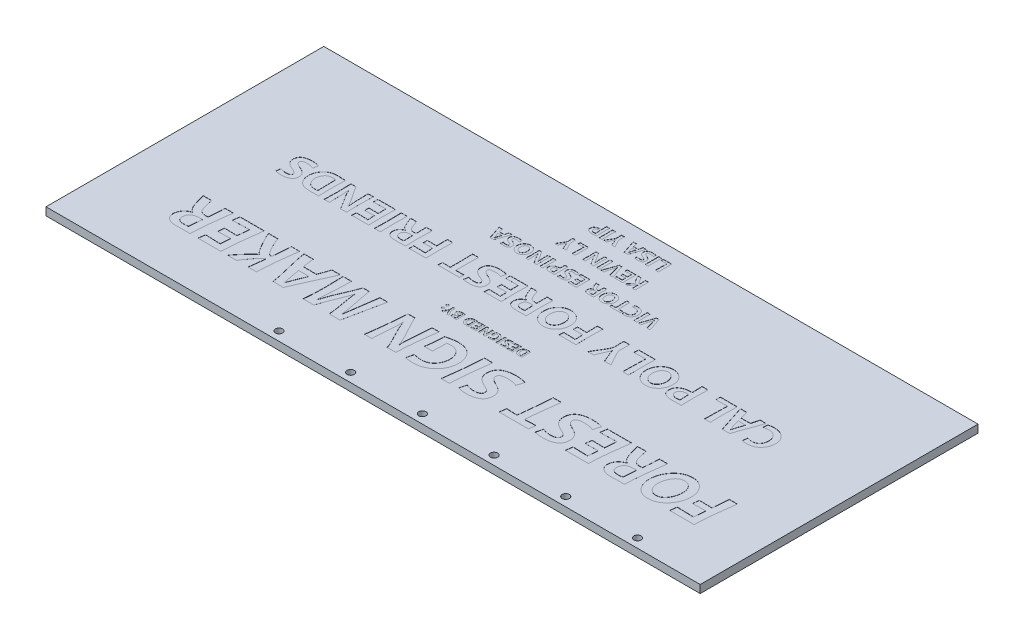
SolidWorks part; units mm, degrees
material "Acrylic (Medium-high impact)"
ref_plane "Front Plane" through (0, 0, 0) normal (0, 0, 1) x (1, 0, 0)
ref_plane "Top Plane" through (0, 0, 0) normal (0, 1, 0) x (1, 0, 0)
ref_plane "Right Plane" through (0, 0, 0) normal (1, 0, 0) x (0, 0, -1)
sketch "Sketch1" plane through (0, 0, 0) normal (0, 1, 0) x (1, 0, 0)
  line L1 (-231.775, 98.425) -> (231.775, 98.425)
  line L2 (-231.775, 98.425) -> (-231.775, -98.425)
  line L3 (-231.775, -98.425) -> (231.775, -98.425)
  line L4 (231.775, 98.425) -> (231.775, -98.425)
  line L5 (-231.775, 98.425) -> (231.775, -98.425) construction
  line L6 (-231.775, -98.425) -> (231.775, 98.425) construction
  point P0 (0, 0)
  dimension "D1" = 463.55
  dimension "D2" = 196.85
extrude "Boss-Extrude1" add sketch "Sketch1" along normal blind 5.588
hole_wizard "#10 Clearance Hole1" positions "Sketch3" profile "Sketch4" hole size "#10" standard "ANSI Inch" end condition up to next
sketch "Sketch3" plane through (0, 5.588, 0) normal (0, 1, 0) x (1, 0, 0)
  line L0 (206.375, -92.075) -> (-185.698, -92.075) construction
  line L2 (231.775, -98.425) -> (231.775, 98.425) construction
  line L3 (-231.775, -98.425) -> (231.775, -98.425) construction
  point P6 (180.975, -92.075)
  point P8 (130.175, -92.075)
  point P10 (79.375, -92.075)
  point P12 (28.575, -92.075)
  point P14 (-22.225, -92.075)
  point P16 (-73.025, -92.075)
  dimension "D1" = 25.4
  dimension "D2" = 6.35
  dimension "D3" = 25.4
  dimension "D4" = 50.8
  dimension "D5" = 50.8
  dimension "D6" = 50.8
  dimension "D7" = 50.8
  dimension "D8" = 50.8
sketch "Sketch4" plane through (180.975, 5.588, 92.075) normal (1, 0, 0) x (0, 0, 1)
  line L0 (0, 0) -> (0, 5.588)
  line L1 (0, 5.588) -> (2.5527, 5.588)
  line L2 (2.5527, 5.588) -> (2.5527, 0)
  line L5 (2.5527, 0) -> (0, 0)
  line L11 (0, -6.35) -> (0, 107.95) construction
  dimension "Thru Hole Dia." = 5.1054
  dimension "Thru Hole Depth" = 5.588
sketch "Sketch5" plane through (0, 5.588, 0) normal (0, 1, 0) x (1, 0, 0)
  line L0 (231.775, -35.8647) -> (-231.775, -35.8647) construction
  line L1 (231.775, 23.746) -> (-231.775, 23.746) construction
  line L2 (231.775, 49.621) -> (-231.775, 49.621) construction
  line L3 (231.775, -98.425) -> (231.775, 98.425) construction
  line L4 (-231.775, 98.425) -> (-231.775, -98.425) construction
  line L5 (231.775, -15.8853) -> (-231.775, -15.8853) construction
  text T0 "<b><i>FOREST SIGN MAKER</i></b>" font "Candara" height 27.94
  text T1 "<b>CAL POLY FOREST FRIENDS</b>" font "Candara" height 19.05
  text T2 "<b>VICTOR ESPINOSA</b>\r\n<b>KEVIN LY</b>\r\n<b>LISA YIP</b>" font "Candara" height 9.525
  text T3 "<b>DESIGNED BY:</b>" font "Candara" height 6.35
extrude "Cut-Extrude1" cut sketch "Sketch5" against normal blind 0.127
